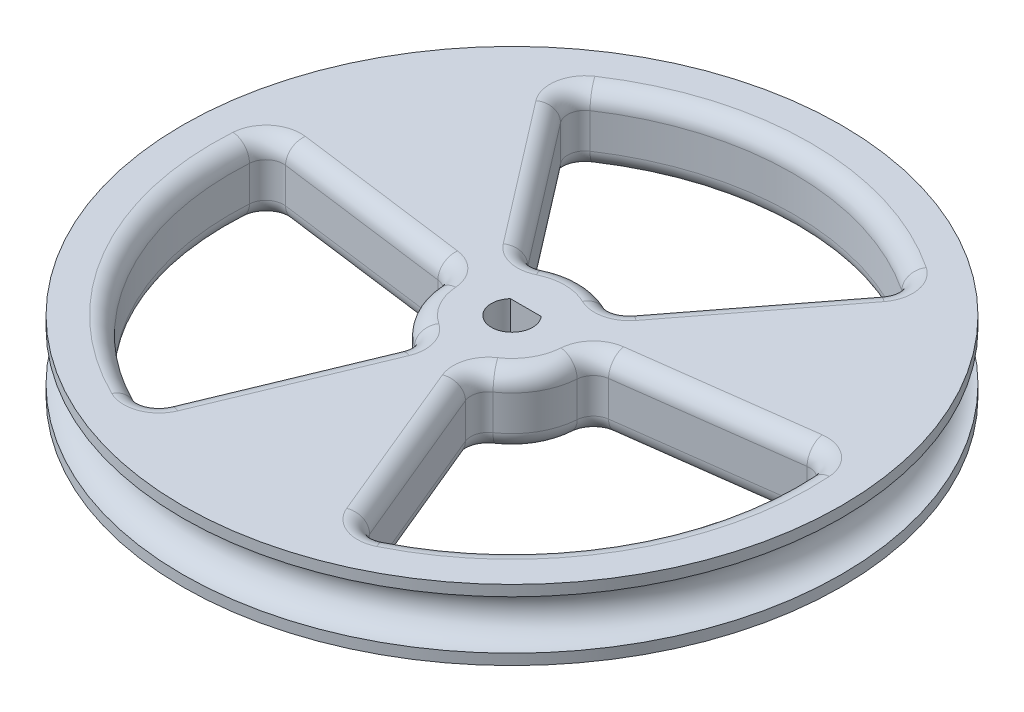
SolidWorks part; units mm, degrees
ref_plane "Front Plane" through (0, 0, 0) normal (0, 0, 1) x (1, 0, 0)
ref_plane "Top Plane" through (0, 0, 0) normal (0, 1, 0) x (1, 0, 0)
ref_plane "Right Plane" through (0, 0, 0) normal (1, 0, 0) x (0, 0, -1)
sketch "Sketch1" plane through (0, 0, 0) normal (0, 1, 0) x (1, 0, 0)
  line L0 (0, 25.5524) -> (0, 22.0218) construction
  circle A0 centre (0, 0) radius 25.5524 construction
  circle A1 centre (0, 0) radius 22.0218 construction
  circle A2 centre (0, 0) radius 23.8156
  circle A3 centre (0, 23.8156) radius 1.7938 construction
  circle A4 centre (0, 0) radius 6.35 construction
  point P34 (0, 0)
  dimension "D1" = 51.1048
  dimension "D2" = 44.0436
extrude "Boss-Extrude1" add sketch "Sketch1" along normal blind 5.08 contours A2
sketch "Sketch2" plane through (0, 5.08, 0) normal (0, 1, 0) x (1, 0, 0)
  line L0 (0, 1.4922) -> (0, -1.4922) construction
  line L1 (-1.1146, 0.9922) -> (1.1146, 0.9922) construction
  line L2 (-1.1146, 0.9922) -> (1.1146, 0.9922)
  arc A0 (-1.1146, 0.9922) -> (1.1146, 0.9922) centre (0, 0) ccw construction
  arc A1 (-1.1146, 0.9922) -> (1.1146, 0.9922) centre (0, 0) ccw
  dimension "D1" = 2.9845
  dimension "D2" = 0.5
extrude "Cut-Extrude1" cut sketch "Sketch2" against normal blind 5.08
sketch "Sketch5" plane through (0, 0, 0) normal (0, 0, 1) x (1, 0, 0)
  line L0 (0, 0) -> (-1.1146, 0)
  line L1 (0, 0) -> (-23.8156, 0) construction
  line L3 (0, 0) -> (-0.2993, -0.2058)
  line L4 (-23.8156, 5.08) -> (-23.8156, 0) construction
  line L7 (-23.8156, 0) -> (-23.8156, 5.08) construction
  line L8 (0, 4.3287) -> (0, 0) construction
  line L9 (-23.8156, 4.3053) -> (-23.8156, 0.7747)
  arc A0 (-23.8156, 0.7747) -> (-23.8156, 4.3053) centre (-23.8156, 2.54) ccw
revolve "Cut-Revolve2" cut sketch "Sketch5" angle 360 about L8
sketch "Sketch8" plane through (0, 5.08, 0) normal (0, 1, 0) x (1, 0, 0)
  line L0 (0, 0) -> (0, 0.9922)
  line L1 (1.1146, 0.9922) -> (-1.1146, 0.9922) construction
  line L2 (0, 0) -> (0, 20.32) construction
  line L3 (0, 0) -> (0, 0.9922)
  line L4 (0, 0) -> (12.37, 16.1209) construction
  line L5 (0, 0) -> (-12.37, 16.1209) construction
  line L6 (3.0925, 4.0302) -> (12.37, 16.1209)
  line L7 (0, 0.9922) -> (0, 0) construction
  line L8 (-12.37, 16.1209) -> (-3.0925, 4.0302)
  circle A0 centre (0, 0) radius 20.32 construction
  circle A1 centre (0, 0) radius 5.08 construction
  arc A2 (-12.37, 16.1209) -> (12.37, 16.1209) centre (0, 0) cw
  arc A3 (-3.0925, 4.0302) -> (3.0925, 4.0302) centre (0, 0) cw
  circle A4 centre (0, 0) radius 23.8156 construction
  dimension "D2" = 37.5
  dimension "D3" = 10.16
  dimension "D4" = 40.64
  dimension "D1" = 75
extrude "Cut-Extrude3" cut sketch "Sketch8" along direction (0, 1, 0) on the side against the normal through all contours L8 A3 L6 A2
fillet "Fillet22" radius 1.27 12 edges at (7.7313, 0, -10.0756) (7.7313, 5.08, -10.0756) (-7.7313, 0, -10.0756) (-7.7313, 5.08, -10.0756) (-3.0925, 2.54, -4.0302) (0, 0, -5.08) (3.0925, 2.54, -4.0302) (0, 5.08, -5.08) (12.37, 2.54, -16.1209) (0, 0, -20.32) (-12.37, 2.54, -16.1209) (0, 5.08, -20.32)
pattern_circular "CirPattern1" count 3 over 360 about axis through (0, 5.08, 0) along (0, 1, 0) of "Cut-Extrude3", "Fillet22"
sketch "Sketch9" plane through (0, 5.08, 0) normal (0, 1, 0) x (1, 0, 0)
  line L0 (-4.0959, -19.05) -> (4.0959, -19.05)
  line L1 (4.0959, -19.05) -> (0, -9.515)
  line L2 (0, -9.515) -> (-4.0959, -19.05)
  line L3 (0, 0) -> (0, -23.8156) construction
  circle A0 centre (0, 0) radius 23.8156 construction
  dimension "D1" = 19.05
